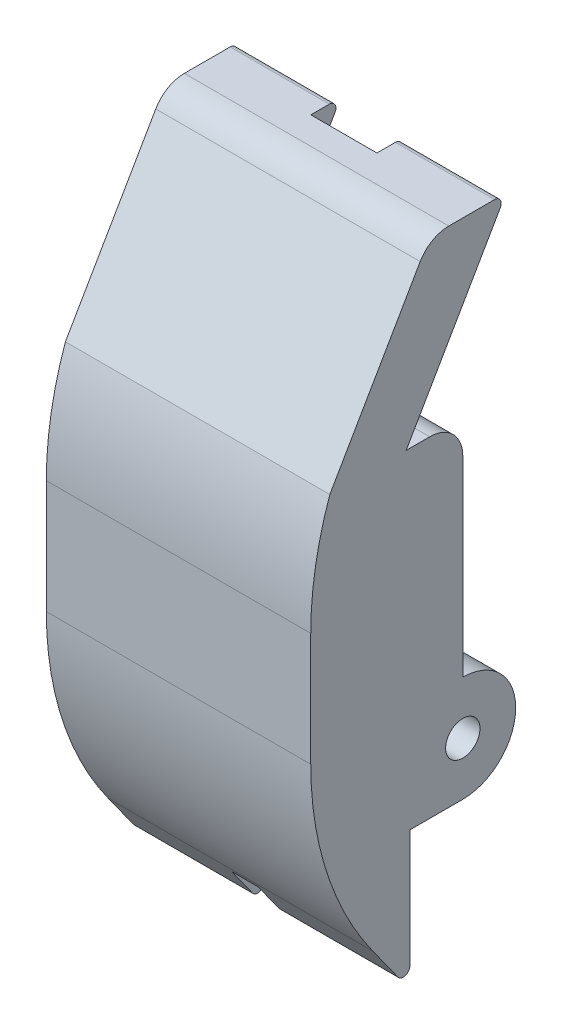
SolidWorks part; units mm, degrees
ref_plane "Front Plane" through (0, 0, 0) normal (0, 0, 1) x (1, 0, 0)
ref_plane "Top Plane" through (0, 0, 0) normal (0, 1, 0) x (1, 0, 0)
ref_plane "Right Plane" through (0, 0, 0) normal (1, 0, 0) x (0, 0, -1)
sketch "Sketch6" plane through (0, 0, 0) normal (1, 0, 0) x (0, 0, -1)
  line L0 (0, 8) -> (0, -8) construction
  line L1 (-23, -8) -> (0, -8)
  line L2 (-23, -8) -> (-23, 42)
  line L5 (0, 8) -> (-13, 8)
  line L6 (-13, 8) -> (-13, 42)
  line L11 (-23, 42) -> (-20.1117, 42)
  line L12 (-20.1117, 42) -> (-5.0041, 68.1671)
  line L13 (-13, 42) -> (-8.5647, 42)
  line L14 (-8.5647, 42) -> (6.5429, 68.1671)
  line L16 (-5.0041, 68.1671) -> (6.5429, 68.1671)
  arc A0 (0, 8) -> (0, -8) centre (0, 0) cw
  circle A1 centre (0, 0) radius 2.6
  point P0 (0, 0)
  dimension "D1" = 5.2
  dimension "D2" = 8
  dimension "D3" = 50
  dimension "D4" = 13
  dimension "D5" = 10
  dimension "D6" = 120
  dimension "D7" = 10
  dimension "D8" = 2.8883
  dimension "D9" = 17.9959
extrude "Boss-Extrude5" add sketch "Sketch6" along normal blind 20 and the other way blind 20
sketch "Sketch7" plane through (0, 8, 0) normal (0, 1, 0) x (1, 0, 0)
  line L1 (-15, -13) -> (15, -13)
  line L2 (-15, -13) -> (-15, 8)
  line L3 (-15, 8) -> (15, 8)
  line L4 (15, -13) -> (15, 8)
  line L5 (20, 8) -> (-20, 8) construction
  line L6 (-20, 0) -> (-20, -13) construction
  line L7 (20, 0) -> (20, -13) construction
  line L8 (-20, -13) -> (20, -13) construction
  point P0 (0, 0)
  dimension "D1" = 5
  dimension "D2" = 5
extrude "Cut-Extrude1" cut sketch "Sketch7" against normal up to surface (16 mm away) up to face at (0, -8, 11.5)
sketch "Sketch9" plane through (20, 0, 0) normal (1, 0, 0) x (0, 0, -1)
  line L0 (-8, -8) -> (-8, -28.8906)
  line L1 (-8, -28.8906) -> (-23, -8)
  line L2 (-23, -8) -> (-8, -8)
  line L3 (-23, -8) -> (0, -8) construction
  dimension "D1" = 15
extrude "Boss-Extrude6" add sketch "Sketch9" against normal offset from surface (18 mm away) 2 up to plane "Right Plane"
mirror "Mirror1" about plane through (0, 0, 0) normal (1, 0, 0) of "Boss-Extrude6"
sketch "Sketch10" plane through (2, 0, 0) normal (-1, 0, 0) x (0, 0, 1)
  line L0 (23, -8) -> (13, -8)
  line L1 (13, -8) -> (13, -21.9271)
  line L2 (13, -21.9271) -> (23, -8)
  line L3 (8, -28.8906) -> (23, -8) construction
extrude "Boss-Extrude7" add sketch "Sketch10" along normal up to surface (4 mm away) up to face at (-2, -13.2227, 13)
sketch "Sketch12" plane through (0, 8, 0) normal (0, 1, 0) x (1, 0, 0)
  line L0 (20, 0) -> (20, -13)
  line L1 (20, -13) -> (15, -13)
  line L2 (15, -13) -> (15, 0)
  line L3 (15, 0) -> (20, 0)
  line L4 (15, -13) -> (20, -13) construction
  line L5 (20, 0) -> (20, -13) construction
  line L6 (15, -13) -> (15, 0) construction
extrude "Boss-Extrude8" add sketch "Sketch12" along normal up to vertex (34 mm away) up to point (20, 42, 13)
mirror "Mirror2" about plane through (0, 0, 0) normal (1, 0, 0) of "Boss-Extrude8"
fillet "Fillet4" radius 5 2 edges at (2, -8, 10.5) (-2, -8, 10.5)
fillet "Fillet5" radius 1 3 edges at (11, -28.8906, 8) (-11, -28.8906, 8) (0, 68.1671, -6.5429)
sketch "Sketch13" plane through (20, 0, 0) normal (1, 0, 0) x (0, 0, -1)
  line L0 (6.5429, 68.1671) -> (-8.5647, 42)
  line L1 (-8.5647, 42) -> (-13.0947, 42)
  line L2 (-13.0947, 42) -> (2.0129, 68.1671)
  line L3 (2.0129, 68.1671) -> (6.5429, 68.1671)
  line L4 (4.8109, 68.1671) -> (-5.0041, 68.1671) construction
  line L5 (-20.1117, 42) -> (-23, 42) construction
  line L6 (-8.5647, 42) -> (5.6769, 66.6671) construction
  point P8 (7.124, 67.9536)
  dimension "D1" = 4.53
extrude "Cut-Extrude3" cut sketch "Sketch13" against normal blind 10 from offset 15 offset against normal yes
sketch "Sketch14" plane through (0, 14.2086, 24.61) normal (0, -0.5, -0.866) x (-1, 0, 0)
  line L0 (-15, 32.0907) -> (-5, 48.7949)
  line L2 (-5, 32.0907) -> (-5, 48.7949)
  line L3 (-5, 32.0907) -> (-5, 60.5738) construction
  line L4 (-15, 32.0907) -> (-15, 29.8731)
  line L5 (-15, 29.8731) -> (-5, 29.8731)
  line L6 (-5, 29.8731) -> (-5, 32.0907)
  line L7 (-5, 29.8731) -> (-15, 29.8731) construction
extrude "Cut-Extrude4" cut sketch "Sketch14" against normal up to surface (3.9231 mm away) up to face at (0, 55.0835, 5.5409)
mirror "Mirror3" about plane through (0, 0, 0) normal (1, 0, 0) of "Cut-Extrude4"
fillet "Fillet7" radius 5 5 edges at (0, 68.1671, 5.0041) (-17.5, 42, 0) (17.5, 42, 0) (-5, 57.447, 1.9113) (5, 57.447, 1.9113)
fillet "Fillet8" radius 50 2 edges at (0, 42, 23) (0, -8, 23)
